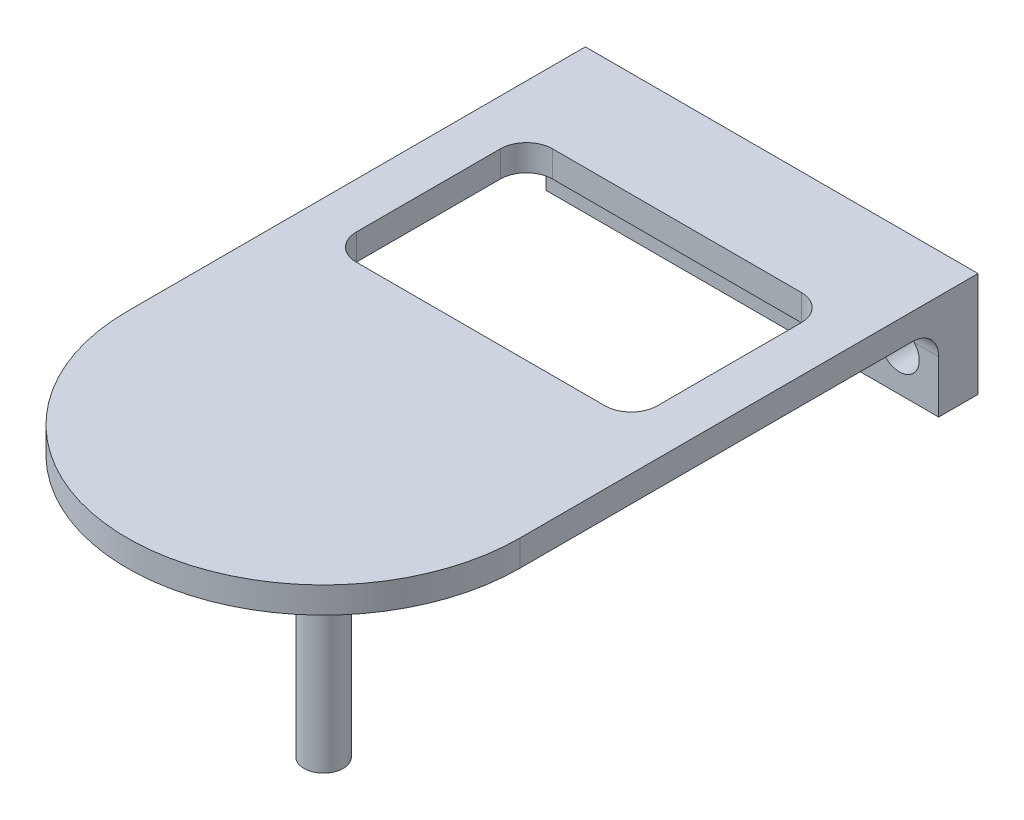
SolidWorks part; units mm, degrees
ref_plane "Front Plane" through (0, 0, 0) normal (0, 0, 1) x (1, 0, 0)
ref_plane "Top Plane" through (0, 0, 0) normal (0, 1, 0) x (1, 0, 0)
ref_plane "Right Plane" through (0, 0, 0) normal (1, 0, 0) x (0, 0, -1)
sketch "Sketch1" plane through (0, 0, 0) normal (0, 1, 0) x (1, 0, 0)
  line L0 (-15, 0) -> (-15, 35)
  line L1 (-15, 35) -> (15, 35)
  line L2 (15, 35) -> (15, 0)
  arc A0 (-15, 0) -> (15, 0) centre (0, 0) ccw
extrude "Boss-Extrude1" add sketch "Sketch1" along normal blind 2
sketch "Sketch2" plane through (0, 0, 0) normal (0, -1, 0) x (1, 0, 0)
  circle A0 centre (0, 0) radius 1.5
extrude "Boss-Extrude2" add sketch "Sketch2" along normal blind 20
sketch "Sketch3" plane through (0, 2, 0) normal (0, 1, 0) x (1, 0, 0)
  line L0 (0, 0) -> (-10, 0) construction
  line L1 (-10, 0) -> (-10, 30) construction
  line L2 (-10, 30) -> (10, 30) construction
  line L3 (10, 30) -> (10, 0) construction
  line L4 (10, 0) -> (0, 0) construction
  line L5 (0, 0) -> (0, 15) construction
  line L6 (0, 15) -> (10, 15) construction
  line L7 (-6, 28.8453) -> (-5, 29.4226)
  line L8 (-10, 28.8453) -> (-9, 29.4226)
  line L9 (-9, 29.4226) -> (-9, 30.5774)
  line L10 (-9, 30.5774) -> (-10, 31.1547)
  line L11 (-10, 31.1547) -> (-11, 30.5774)
  line L12 (-11, 30.5774) -> (-11, 29.4226)
  line L13 (-11, 29.4226) -> (-10, 28.8453)
  line L14 (-5, 29.4226) -> (-5, 30.5774)
  line L15 (-5, 30.5774) -> (-6, 31.1547)
  line L16 (-6, 31.1547) -> (-7, 30.5774)
  line L17 (-7, 30.5774) -> (-7, 29.4226)
  line L18 (-7, 29.4226) -> (-6, 28.8453)
  line L19 (-2, 28.8453) -> (-1, 29.4226)
  line L20 (-1, 29.4226) -> (-1, 30.5774)
  line L21 (-1, 30.5774) -> (-2, 31.1547)
  line L22 (-2, 31.1547) -> (-3, 30.5774)
  line L23 (-3, 30.5774) -> (-3, 29.4226)
  line L24 (-3, 29.4226) -> (-2, 28.8453)
  line L25 (2, 28.8453) -> (3, 29.4226)
  line L26 (3, 29.4226) -> (3, 30.5774)
  line L27 (3, 30.5774) -> (2, 31.1547)
  line L28 (2, 31.1547) -> (1, 30.5774)
  line L29 (1, 30.5774) -> (1, 29.4226)
  line L30 (1, 29.4226) -> (2, 28.8453)
  line L31 (6, 28.8453) -> (7, 29.4226)
  line L32 (7, 29.4226) -> (7, 30.5774)
  line L33 (7, 30.5774) -> (6, 31.1547)
  line L34 (6, 31.1547) -> (5, 30.5774)
  line L35 (5, 30.5774) -> (5, 29.4226)
  line L36 (5, 29.4226) -> (6, 28.8453)
  line L37 (10, 28.8453) -> (11, 29.4226)
  line L38 (11, 29.4226) -> (11, 30.5774)
  line L39 (11, 30.5774) -> (10, 31.1547)
  line L40 (10, 31.1547) -> (9, 30.5774)
  line L41 (9, 30.5774) -> (9, 29.4226)
  line L42 (9, 29.4226) -> (10, 28.8453)
  line L43 (-6, 24.8453) -> (-5, 25.4226)
  line L44 (-5, 25.4226) -> (-5, 26.5774)
  line L45 (-5, 26.5774) -> (-6, 27.1547)
  line L46 (-6, 27.1547) -> (-7, 26.5774)
  line L47 (-7, 26.5774) -> (-7, 25.4226)
  line L48 (-7, 25.4226) -> (-6, 24.8453)
  line L49 (-2, 24.8453) -> (-1, 25.4226)
  line L50 (-1, 25.4226) -> (-1, 26.5774)
  line L51 (-1, 26.5774) -> (-2, 27.1547)
  line L52 (-2, 27.1547) -> (-3, 26.5774)
  line L53 (-3, 26.5774) -> (-3, 25.4226)
  line L54 (-3, 25.4226) -> (-2, 24.8453)
  line L55 (2, 24.8453) -> (3, 25.4226)
  line L56 (3, 25.4226) -> (3, 26.5774)
  line L57 (3, 26.5774) -> (2, 27.1547)
  line L58 (2, 27.1547) -> (1, 26.5774)
  line L59 (1, 26.5774) -> (1, 25.4226)
  line L60 (1, 25.4226) -> (2, 24.8453)
  line L61 (6, 24.8453) -> (7, 25.4226)
  line L62 (7, 25.4226) -> (7, 26.5774)
  line L63 (7, 26.5774) -> (6, 27.1547)
  line L64 (6, 27.1547) -> (5, 26.5774)
  line L65 (5, 26.5774) -> (5, 25.4226)
  line L66 (5, 25.4226) -> (6, 24.8453)
  line L67 (10, 24.8453) -> (11, 25.4226)
  line L68 (11, 25.4226) -> (11, 26.5774)
  line L69 (11, 26.5774) -> (10, 27.1547)
  line L70 (10, 27.1547) -> (9, 26.5774)
  line L71 (9, 26.5774) -> (9, 25.4226)
  line L72 (9, 25.4226) -> (10, 24.8453)
  line L73 (-6, 20.8453) -> (-5, 21.4226)
  line L74 (-5, 21.4226) -> (-5, 22.5774)
  line L75 (-5, 22.5774) -> (-6, 23.1547)
  line L76 (-6, 23.1547) -> (-7, 22.5774)
  line L77 (-7, 22.5774) -> (-7, 21.4226)
  line L78 (-7, 21.4226) -> (-6, 20.8453)
  line L79 (-2, 20.8453) -> (-1, 21.4226)
  line L80 (-1, 21.4226) -> (-1, 22.5774)
  line L81 (-1, 22.5774) -> (-2, 23.1547)
  line L82 (-2, 23.1547) -> (-3, 22.5774)
  line L83 (-3, 22.5774) -> (-3, 21.4226)
  line L84 (-3, 21.4226) -> (-2, 20.8453)
  line L85 (2, 20.8453) -> (3, 21.4226)
  line L86 (3, 21.4226) -> (3, 22.5774)
  line L87 (3, 22.5774) -> (2, 23.1547)
  line L88 (2, 23.1547) -> (1, 22.5774)
  line L89 (1, 22.5774) -> (1, 21.4226)
  line L90 (1, 21.4226) -> (2, 20.8453)
  line L91 (6, 20.8453) -> (7, 21.4226)
  line L92 (7, 21.4226) -> (7, 22.5774)
  line L93 (7, 22.5774) -> (6, 23.1547)
  line L94 (6, 23.1547) -> (5, 22.5774)
  line L95 (5, 22.5774) -> (5, 21.4226)
  line L96 (5, 21.4226) -> (6, 20.8453)
  line L97 (10, 20.8453) -> (11, 21.4226)
  line L98 (11, 21.4226) -> (11, 22.5774)
  line L99 (11, 22.5774) -> (10, 23.1547)
  line L100 (10, 23.1547) -> (9, 22.5774)
  line L101 (9, 22.5774) -> (9, 21.4226)
  line L102 (9, 21.4226) -> (10, 20.8453)
  line L103 (-6, 16.8453) -> (-5, 17.4226)
  line L104 (-5, 17.4226) -> (-5, 18.5774)
  line L105 (-5, 18.5774) -> (-6, 19.1547)
  line L106 (-6, 19.1547) -> (-7, 18.5774)
  line L107 (-7, 18.5774) -> (-7, 17.4226)
  line L108 (-7, 17.4226) -> (-6, 16.8453)
  line L109 (-2, 16.8453) -> (-1, 17.4226)
  line L110 (-1, 17.4226) -> (-1, 18.5774)
  line L111 (-1, 18.5774) -> (-2, 19.1547)
  line L112 (-2, 19.1547) -> (-3, 18.5774)
  line L113 (-3, 18.5774) -> (-3, 17.4226)
  line L114 (-3, 17.4226) -> (-2, 16.8453)
  line L115 (2, 16.8453) -> (3, 17.4226)
  line L116 (3, 17.4226) -> (3, 18.5774)
  line L117 (3, 18.5774) -> (2, 19.1547)
  line L118 (2, 19.1547) -> (1, 18.5774)
  line L119 (1, 18.5774) -> (1, 17.4226)
  line L120 (1, 17.4226) -> (2, 16.8453)
  line L121 (6, 16.8453) -> (7, 17.4226)
  line L122 (7, 17.4226) -> (7, 18.5774)
  line L123 (7, 18.5774) -> (6, 19.1547)
  line L124 (6, 19.1547) -> (5, 18.5774)
  line L125 (5, 18.5774) -> (5, 17.4226)
  line L126 (5, 17.4226) -> (6, 16.8453)
  line L127 (10, 16.8453) -> (11, 17.4226)
  line L128 (11, 17.4226) -> (11, 18.5774)
  line L129 (11, 18.5774) -> (10, 19.1547)
  line L130 (10, 19.1547) -> (9, 18.5774)
  line L131 (9, 18.5774) -> (9, 17.4226)
  line L132 (9, 17.4226) -> (10, 16.8453)
  line L133 (-6, 12.8453) -> (-5, 13.4226)
  line L134 (-5, 13.4226) -> (-5, 14.5774)
  line L135 (-5, 14.5774) -> (-6, 15.1547)
  line L136 (-6, 15.1547) -> (-7, 14.5774)
  line L137 (-7, 14.5774) -> (-7, 13.4226)
  line L138 (-7, 13.4226) -> (-6, 12.8453)
  line L139 (-2, 12.8453) -> (-1, 13.4226)
  line L140 (-1, 13.4226) -> (-1, 14.5774)
  line L141 (-1, 14.5774) -> (-2, 15.1547)
  line L142 (-2, 15.1547) -> (-3, 14.5774)
  line L143 (-3, 14.5774) -> (-3, 13.4226)
  line L144 (-3, 13.4226) -> (-2, 12.8453)
  line L145 (2, 12.8453) -> (3, 13.4226)
  line L146 (3, 13.4226) -> (3, 14.5774)
  line L147 (3, 14.5774) -> (2, 15.1547)
  line L148 (2, 15.1547) -> (1, 14.5774)
  line L149 (1, 14.5774) -> (1, 13.4226)
  line L150 (1, 13.4226) -> (2, 12.8453)
  line L151 (6, 12.8453) -> (7, 13.4226)
  line L152 (7, 13.4226) -> (7, 14.5774)
  line L153 (7, 14.5774) -> (6, 15.1547)
  line L154 (6, 15.1547) -> (5, 14.5774)
  line L155 (5, 14.5774) -> (5, 13.4226)
  line L156 (5, 13.4226) -> (6, 12.8453)
  line L157 (10, 12.8453) -> (11, 13.4226)
  line L158 (11, 13.4226) -> (11, 14.5774)
  line L159 (11, 14.5774) -> (10, 15.1547)
  line L160 (10, 15.1547) -> (9, 14.5774)
  line L161 (9, 14.5774) -> (9, 13.4226)
  line L162 (9, 13.4226) -> (10, 12.8453)
  line L163 (-10, 24.8453) -> (-9, 25.4226)
  line L164 (-9, 25.4226) -> (-9, 26.5774)
  line L165 (-9, 26.5774) -> (-10, 27.1547)
  line L166 (-10, 27.1547) -> (-11, 26.5774)
  line L167 (-11, 26.5774) -> (-11, 25.4226)
  line L168 (-11, 25.4226) -> (-10, 24.8453)
  line L169 (-10, 20.8453) -> (-9, 21.4226)
  line L170 (-9, 21.4226) -> (-9, 22.5774)
  line L171 (-9, 22.5774) -> (-10, 23.1547)
  line L172 (-10, 23.1547) -> (-11, 22.5774)
  line L173 (-11, 22.5774) -> (-11, 21.4226)
  line L174 (-11, 21.4226) -> (-10, 20.8453)
  line L175 (-10, 16.8453) -> (-9, 17.4226)
  line L176 (-9, 17.4226) -> (-9, 18.5774)
  line L177 (-9, 18.5774) -> (-10, 19.1547)
  line L178 (-10, 19.1547) -> (-11, 18.5774)
  line L179 (-11, 18.5774) -> (-11, 17.4226)
  line L180 (-11, 17.4226) -> (-10, 16.8453)
  line L181 (-10, 12.8453) -> (-9, 13.4226)
  line L182 (-9, 13.4226) -> (-9, 14.5774)
  line L183 (-9, 14.5774) -> (-10, 15.1547)
  line L184 (-10, 15.1547) -> (-11, 14.5774)
  line L185 (-11, 14.5774) -> (-11, 13.4226)
  line L186 (-11, 13.4226) -> (-10, 12.8453)
  circle A0 centre (-10, 30) radius 1 construction
  dimension "D1" = 6
  dimension "D2" = 5
extrude "Cut-Extrude1" [suppressed] cut sketch "Sketch3" against normal blind 20
sketch "Sketch4" plane through (0, 0, -35) normal (0, 0, -1) x (-1, 0, 0)
  line L0 (-15, 2) -> (15, 2)
  line L1 (15, 2) -> (15, -6)
  line L2 (15, -6) -> (-15, -6)
  line L3 (-15, -6) -> (-15, 2)
  dimension "D1" = 8
extrude "Boss-Extrude3" add sketch "Sketch4" against normal blind 3
sketch "Sketch5" plane through (0, 0, -35) normal (0, 0, -1) x (-1, 0, 0)
  line L0 (-15, 2) -> (-15, -6) construction
  line L1 (-15, -6) -> (15, -6) construction
  line L2 (15, 2) -> (15, -6) construction
  circle A0 centre (-12, -3) radius 1.51
  circle A1 centre (12, -3) radius 1.51
  dimension "D1" = 3
  dimension "D2" = 3
  dimension "D3" = 3
  dimension "D4" = 3
extrude "Cut-Extrude2" cut sketch "Sketch5" against normal blind 3
sketch "Sketch6" plane through (0, 0, 0) normal (0, -1, 0) x (1, 0, 0)
  line L1 (11.5, -12) -> (-11.5, -12)
  line L2 (11.5, -12) -> (11.5, -27)
  line L3 (11.5, -27) -> (-11.5, -27)
  line L4 (-11.5, -12) -> (-11.5, -27)
  line L5 (11.5, -12) -> (-11.5, -27) construction
  line L6 (11.5, -27) -> (-11.5, -12) construction
  line L7 (15, 0) -> (15, -32) construction
  line L9 (15, -32) -> (-15, -32) construction
  point P0 (0, -19.5)
  dimension "D1" = 23
  dimension "D2" = 3.5
  dimension "D3" = 15
  dimension "D4" = 5
extrude "Cut-Extrude3" cut sketch "Sketch6" against normal blind 10
fillet "Fillet1" radius 2 1 edges at (0, 0, -32)
fillet "Fillet2" radius 2 4 edges at (-11.5, 1, -12) (-11.5, 1, -27) (11.5, 1, -12) (11.5, 1, -27)
